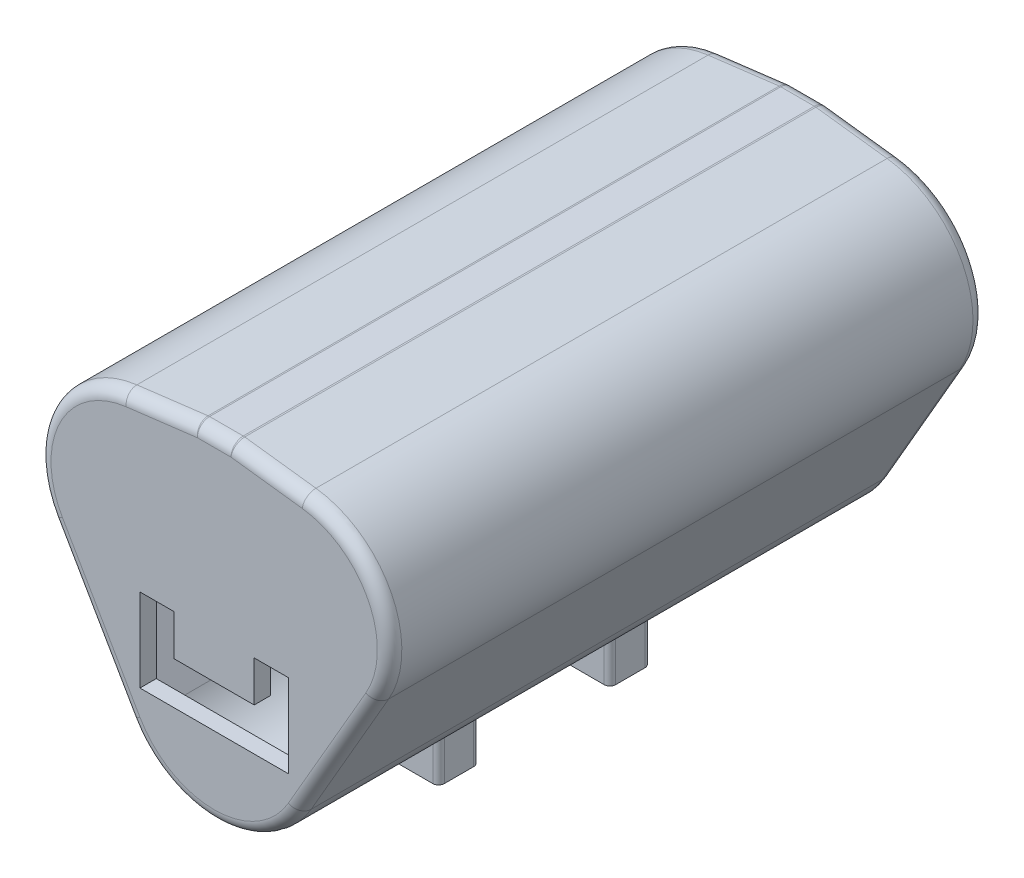
SolidWorks part; units mm, degrees
ref_plane "Front Plane" through (0, 0, 0) normal (0, 0, 1) x (1, 0, 0)
ref_plane "Top Plane" through (0, 0, 0) normal (0, 1, 0) x (1, 0, 0)
ref_plane "Right Plane" through (0, 0, 0) normal (1, 0, 0) x (0, 0, -1)
sketch "Sketch1" plane through (0, 0, 0) normal (0, 0, 1) x (1, 0, 0)
  line L0 (0, 0) -> (119.5956, 0) construction
  line L1 (0, 0) -> (0, 75.1119) construction
  line L2 (0, 0) -> (73.6256, 42.5077) construction
  line L3 (0, 0) -> (-73.6256, 42.5077) construction
  line L4 (8.2272, -15.7197) -> (17.7272, 0.7348)
  line L5 (-8.2272, -15.7197) -> (-17.7272, 0.7348)
  line L6 (-2, 15.9848) -> (2, 15.9848)
  line L7 (2, 15.9848) -> (10.6661, 14.913)
  line L8 (-2, 15.9848) -> (-10.6661, 14.913)
  line L9 (-44.9553, 14.9848) -> (50.9395, 14.9848) construction
  line L10 (2.154, 18.4848) -> (10.973, 17.3941)
  line L11 (-2.154, 18.4848) -> (2.154, 18.4848)
  line L12 (-2.154, 18.4848) -> (-10.973, 17.3941)
  line L13 (10.3923, -16.9697) -> (19.8923, -0.5152)
  line L14 (-10.3923, -16.9697) -> (-19.8923, -0.5152)
  line L15 (2.0308, 16.4848) -> (10.7275, 15.4092)
  line L16 (-2.0308, 16.4848) -> (2.0308, 16.4848)
  line L17 (-2.0308, 16.4848) -> (-10.7275, 15.4092)
  line L18 (8.6603, -15.9697) -> (18.1603, 0.4848)
  line L19 (-8.6603, -15.9697) -> (-18.1603, 0.4848)
  circle A0 centre (0, 0) radius 10.9697 construction
  circle A1 centre (9.5, 5.4848) radius 9.5
  circle A2 centre (0, -10.9697) radius 9.5
  circle A3 centre (-9.5, 5.4848) radius 9.5
  arc A4 (-10.3923, -16.9697) -> (10.3923, -16.9697) centre (0, -10.9697) ccw
  arc A5 (19.8923, -0.5152) -> (10.973, 17.3941) centre (9.5, 5.4848) ccw
  arc A6 (-19.8923, -0.5152) -> (-10.973, 17.3941) centre (-9.5, 5.4848) cw
  arc A7 (18.1603, 0.4848) -> (10.7275, 15.4092) centre (9.5, 5.4848) ccw
  arc A8 (-18.1603, 0.4848) -> (-10.7275, 15.4092) centre (-9.5, 5.4848) cw
  arc A9 (-8.6603, -15.9697) -> (8.6603, -15.9697) centre (0, -10.9697) ccw
  dimension "D2" = 19
  dimension "D1" = 30
  dimension "D3" = 4
  dimension "D4" = 1
  dimension "D5" = 2.5
  dimension "D6" = 2.5
  dimension "D7" = 2
extrude "Boss-Extrude1" add sketch "Sketch1" along normal blind 36.5 and the other way blind 36.5 contours A6 L14 A4 L13 A5 L10 L11 L12 A3 L8 L6 L7 A1 L4 A2 L5 region at (6.4902, 17.3467, 0)
extrude "Boss-Extrude3" add sketch "Sketch1<5>" against normal offset from surface 4 and the other way up to surface (36.5 mm away) contours L19 A9 L18 A7 L15 L16 L17 A8 A3 L8 L6 L7 A1 L4 A2 L5 region at (6.3725, 15.8934, 0) up to face at (0, 3.9763, -36.5) other way up to face at (0, 3.9763, 36.5)
sketch "Sketch1<5>" plane through (0, 0, 0) normal (0, 0, 1) x (1, 0, 0) same geometry as "Sketch1"
extrude "Boss-Extrude2" add sketch "Sketch1<3>" against normal blind 2 from surface contours A3 | A1 | A3 A2 A1 | A2 | A3 A1 L7 L6 L8 | A2 L4 A1 | A3 L5 A2 region at (11.1395, -6.4314, 0) region at (0, -10.9697, 0) region at (9.5, 5.4848, 0) region at (-11.1395, -6.4314, 0) region at (0, 0, 0) region at (-9.5, 5.4848, 0) region at (0, 13.4602, 0) starting at face at (0, 4.4473, 36.5)
sketch "Sketch1<3>" plane through (0, 0, 0) normal (0, 0, 1) x (1, 0, 0) same geometry as "Sketch1"
sketch "Sketch2" plane through (0, 0, 0) normal (0, 1, 0) x (1, 0, 0)
  line L0 (-3, 36.5) -> (-3, 31.5)
  line L2 (-3, 31.5) -> (3, 31.5)
  line L4 (3, 31.5) -> (3, 36.5)
  line L5 (3, 36.5) -> (-3, 36.5)
  line L8 (0, 0) -> (0, 160.4863) construction
  line L10 (-4.5, 36.5) -> (4.5, 36.5) construction
  dimension "D1" = 5
  dimension "D2" = 6
extrude "Cut-Extrude1" cut sketch "Sketch2" against normal through all contours L4 L5 L0 L2 | L2 L8 L5 L0 region at (-1.5, 0, -34) region at (1.5, 0, -34)
sketch "Sketch3" plane through (0, 0, 36.5) normal (0, 0, 1) x (1, 0, 0)
  line L0 (-9, -3) -> (-9, -13) construction
  line L1 (-9, -13) -> (9, -13) construction
  line L2 (9, -13) -> (9, -3) construction
  line L3 (9, -3) -> (5, -3) construction
  line L4 (5, -3) -> (5, -8) construction
  line L5 (-19.8923, -0.5152) -> (-10.3923, -16.9697)
  line L6 (10.3923, -16.9697) -> (19.8923, -0.5152)
  line L7 (10.973, 17.3941) -> (2.154, 18.4848)
  line L8 (2.154, 18.4848) -> (-2.154, 18.4848)
  line L9 (-2.154, 18.4848) -> (-10.973, 17.3941)
  line L10 (-19.8923, -0.5152) -> (-10.3923, -16.9697)
  line L11 (10.3923, -16.9697) -> (19.8923, -0.5152)
  line L12 (10.973, 17.3941) -> (2.154, 18.4848)
  line L13 (2.154, 18.4848) -> (-2.154, 18.4848)
  line L14 (-2.154, 18.4848) -> (-10.973, 17.3941)
  line L15 (5, -8) -> (-5, -8) construction
  line L16 (-5, -8) -> (-5, -3) construction
  line L17 (-5, -3) -> (-9, -3) construction
  line L18 (-9.1, -2.9) -> (-9.1, -13.1)
  line L19 (-9.1, -13.1) -> (9.1, -13.1)
  line L20 (9.1, -13.1) -> (9.1, -2.9)
  line L21 (9.1, -2.9) -> (4.9, -2.9)
  line L22 (4.9, -2.9) -> (4.9, -7.9)
  line L23 (4.9, -7.9) -> (-4.9, -7.9)
  line L24 (-4.9, -7.9) -> (-4.9, -2.9)
  line L25 (-4.9, -2.9) -> (-9.1, -2.9)
  arc A3 (-10.973, 17.3941) -> (-19.8923, -0.5152) centre (-9.5, 5.4848) ccw
  arc A4 (-10.3923, -16.9697) -> (10.3923, -16.9697) centre (0, -10.9697) ccw
  arc A5 (19.8923, -0.5152) -> (10.973, 17.3941) centre (9.5, 5.4848) ccw
  arc A6 (-10.973, 17.3941) -> (-19.8923, -0.5152) centre (-9.5, 5.4848) ccw
  arc A7 (-10.3923, -16.9697) -> (10.3923, -16.9697) centre (0, -10.9697) ccw
  arc A8 (19.8923, -0.5152) -> (10.973, 17.3941) centre (9.5, 5.4848) ccw
  dimension "D1" = 0
  dimension "D2" = 0.1
extrude "Cut-Extrude2" cut sketch "Sketch3" against normal blind 2 contours L18 L19 L20 L21 L22 L23 L24 L25
ref_plane "Plane1" through (0, -29, 0) normal (0, 1, 0) x (1, 0, 0)
sketch "Sketch4" plane through (0, -29, 0) normal (0, 1, 0) x (1, 0, 0)
  line L0 (0, 0) -> (0, 66.2567) construction
  line L1 (-200000, 0) -> (200119.5956, 0) construction
  line L2 (-4, -8) -> (4, -8)
  line L3 (-4, -8) -> (-4, -13)
  line L4 (-4, -13) -> (4, -13)
  line L5 (4, -8) -> (4, -13)
  line L7 (0, 0) -> (75.5127, 0) construction
  line L8 (4, 8) -> (4, 13)
  line L9 (-4, 13) -> (4, 13)
  line L10 (-4, 8) -> (-4, 13)
  line L11 (-4, 8) -> (4, 8)
  dimension "D1" = 8
  dimension "D2" = 5
  dimension "D3" = 8
extrude "Boss-Extrude4" add sketch "Sketch4" along normal up to next from offset 0.2 contours L10 L11 L8 L9 | L5 L2 L3 L4 region at (0, -29, 10.5) region at (0, -29, -10.5)
fillet "Fillet1" radius 1.5 21 edges at (-6.5635, 17.9395, 36.5) (-20.2416, 10.8345, 36.5) (-15.1423, -8.7424, 36.5) (0, -22.9697, 36.5) (15.1423, -8.7424, 36.5) (6.5635, 17.9395, 36.5) (-7.2617, -20.5231, -36.5) (-15.1423, -8.7424, -36.5) (-20.2416, 10.8345, -36.5) (7.2617, -20.5231, -36.5) (15.1423, -8.7424, -36.5) (20.2416, 10.8345, -36.5) (-2, 15.9848, 1) (2, 15.9848, 1) (-2.154, 18.4848, 0) (2.154, 18.4848, 0) (0, 18.4848, -36.5) (0, 18.4848, 36.5) (20.2416, 10.8345, 36.5) (-6.5635, 17.9395, -36.5) (6.5635, 17.9395, -36.5)
fillet "Fillet2" radius 0.7 13 edges at (3, -19.9835, -32) (-3, -19.9835, -32) (0, -20.4697, -31.5) (-3, -21.2861, -31.5) (3, -21.2861, -31.5) (-4, -25.5417, -13) (-4, -25.5417, -8) (-4, -25.5417, 8) (-4, -25.5417, 13) (4, -25.5417, 13) (4, -25.5417, 8) (4, -25.5417, -8) (4, -25.5417, -13)
fillet "Fillet3" radius 0.7 9 edges at (3, -20.7705, -36.5) (3, -22.0354, -36.1482) (3, -22.5886, -33.6) (2.7446, -22.6516, -31.6594) (-3, -20.7705, -36.5) (-3, -22.2676, -35.9139) (-3, -22.5886, -33.6) (-2.8543, -22.6253, -31.7725) (0, -22.9697, -31.5)
